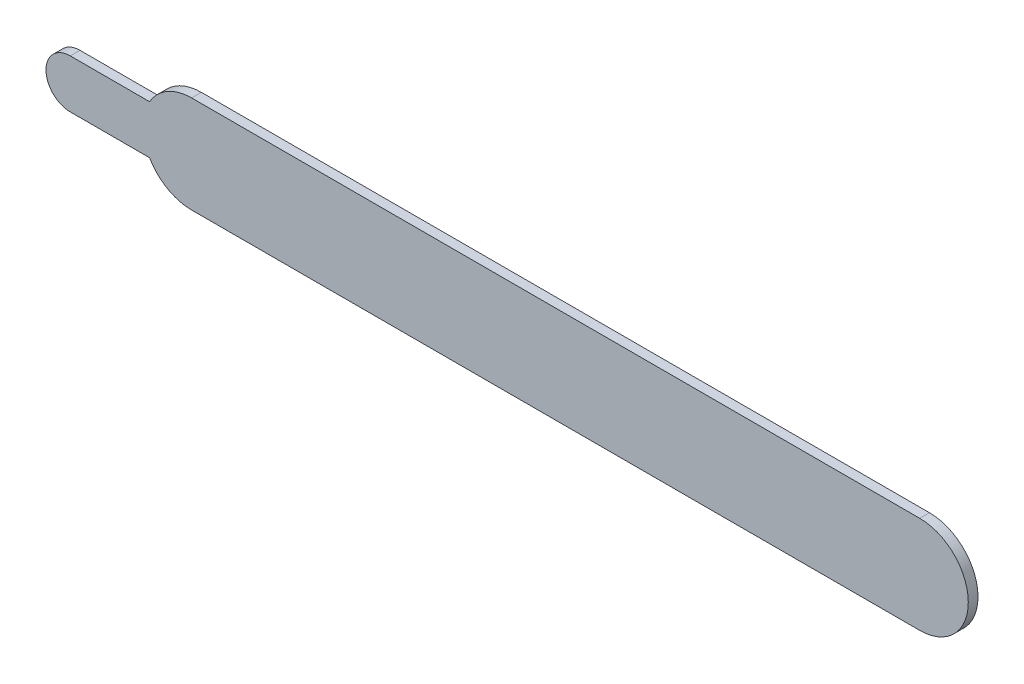
SolidWorks part; units mm, degrees
ref_plane "Front Plane" through (0, 0, 0) normal (0, 0, 1) x (1, 0, 0)
ref_plane "Top Plane" through (0, 0, 0) normal (0, 1, 0) x (1, 0, 0)
ref_plane "Right Plane" through (0, 0, 0) normal (1, 0, 0) x (0, 0, -1)
sketch "Sketch1" plane through (0, 0, 0) normal (0, 0, 1) x (1, 0, 0)
  line L1 (0, 10) -> (150, 10)
  line L2 (0, -10) -> (150, -10)
  line L3 (0, 0) -> (-25, 0) construction
  line L8 (-8.6603, -5) -> (-25, -5)
  line L9 (-8.6603, 5) -> (-25, 5)
  line L10 (150, 10) -> (150, -14.8875) construction
  arc A0 (0, 10) -> (-8.6603, 5) centre (0, 0) ccw
  arc A1 (150, -10) -> (150, 10) centre (150, 0) ccw
  arc A3 (-25, 5) -> (-25, -5) centre (-25, 0) ccw
  arc A4 (-8.6603, -5) -> (0, -10) centre (0, 0) ccw
  point P3 (50, 0)
  point P8 (0, 0)
  point P10 (-12.5, 0)
  point P11 (0, 0)
  point P15 (0, 0)
  point P18 (146.4707, -11.856)
  point P19 (140.1267, 8.2259)
  point P20 (0, 0)
  point P21 (139.9993, -10)
  point P22 (139.9994, 0)
  point P23 (140, 0)
  point P24 (140, 0)
  point P25 (0, 0)
  point P26 (140, -10)
  point P27 (140, 10)
  dimension "D1" = 10
  dimension "D3" = 5
  dimension "D2" = 150
  dimension "D4" = 25
  dimension "D5" = 20
extrude "Boss-Extrude1" add sketch "Sketch1" along normal mid plane 2
